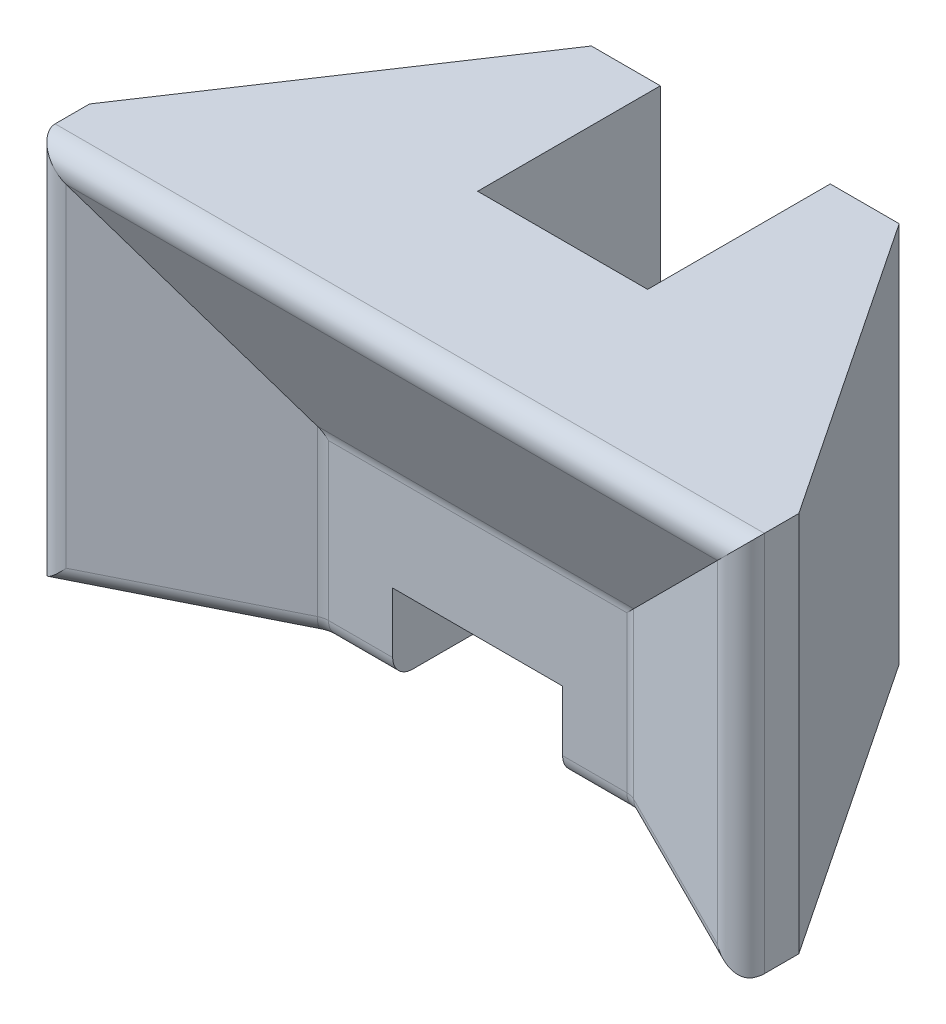
SolidWorks part; units mm, degrees
note: The reader was unsure of these and kept them because the rebuilt part matched: shared geometry of "Sketch5<3>".
material "ABS"
ref_plane "Front Plane" through (0, 0, 0) normal (0, 0, 1) x (1, 0, 0)
ref_plane "Top Plane" through (0, 0, 0) normal (0, 1, 0) x (1, 0, 0)
ref_plane "Right Plane" through (0, 0, 0) normal (1, 0, 0) x (0, 0, -1)
sketch "Sketch1" plane through (0, 0, 0) normal (0, 0, 1) x (1, 0, 0)
  line L0 (23, -13.5) -> (53, -13.5)
  line L2 (-23, -13.5) -> (-23, 13.5)
  line L3 (-23, 13.5) -> (23, 13.5)
  line L4 (23, -13.5) -> (23, 13.5)
  line L5 (-23, -13.5) -> (23, 13.5) construction
  line L6 (-23, 13.5) -> (23, -13.5) construction
  line L7 (-53, -13.5) -> (-23, -13.5)
  line L8 (-53, -13.5) -> (-53, 43.5)
  line L9 (-53, 43.5) -> (53, 43.5)
  line L10 (53, -13.5) -> (53, 43.5)
  line L11 (-23, 13.5) -> (-23, 43.5) construction
  point P0 (0, 0)
  dimension "D1" = 46
  dimension "D2" = 30
  dimension "D3" = 27
extrude "Boss-Extrude1" add sketch "Sketch1" along normal blind 15
chamfer "Chamfer1" distance 15 distance2 30 3 edges at (23, 0, 15) (0, 13.5, 15) (-23, 0, 15)
sketch "Sketch4" plane through (0, 0, 0) normal (0, 0, -1) x (-1, 0, 0)
  line L1 (-53, 43.5) -> (53, 43.5)
  line L2 (-53, 43.5) -> (-53, -13.5)
  line L3 (-53, -13.5) -> (53, -13.5)
  line L4 (53, 43.5) -> (53, -13.5)
extrude "Boss-Extrude3" add sketch "Sketch4" along normal blind 40
sketch "Sketch5" plane through (0, -13.5, 0) normal (0, -1, 0) x (1, 0, 0)
  line L0 (23, 0) -> (-23, 0) construction
  line L1 (-12.7, 0) -> (12.7, 0)
  line L2 (-12.7, 0) -> (-12.7, -12.7)
  line L3 (-12.7, -12.7) -> (12.7, -12.7)
  line L4 (12.7, 0) -> (12.7, -12.7)
  line L5 (53, -40) -> (-53, -40) construction
  line L6 (-12.7, -12.7) -> (12.7, -12.7)
  line L7 (-12.7, -12.7) -> (-12.7, -40)
  line L8 (-12.7, -40) -> (12.7, -40)
  line L9 (12.7, -12.7) -> (12.7, -40)
  point P6 (0, 0)
  line M6 (-53, -40) -> (53, -40)
  line M9 (23, 0) -> (-23, 0)
  dimension "D1" = 25.4
  dimension "D2" = 12.7
extrude "Cut-Extrude3" cut sketch "Sketch5" against normal blind 12 contours L4 L2 L3 M9
extrude "Cut-Extrude4" cut sketch "Sketch5<3>" against normal through all contours L9 L3 L7 M6
sketch "Sketch5<3>" plane through (0, -13.5, 0) normal (0, -1, 0) x (1, 0, 0) same geometry as "Sketch5"
chamfer "Chamfer3" distance 45 distance2 30 2 edges at (53, 15, -40) (-53, 15, -40)
fillet "Fillet2" radius 3 10 edges at (23, 0, 0) (0, 13.5, 0) (-23, 0, 0) (-38, -13.5, 7.5) (-17.85, -13.5, 0) (17.85, -13.5, 0) (38, -13.5, 7.5) (53, 15, 15) (0, 43.5, 15) (-53, 15, 15)
